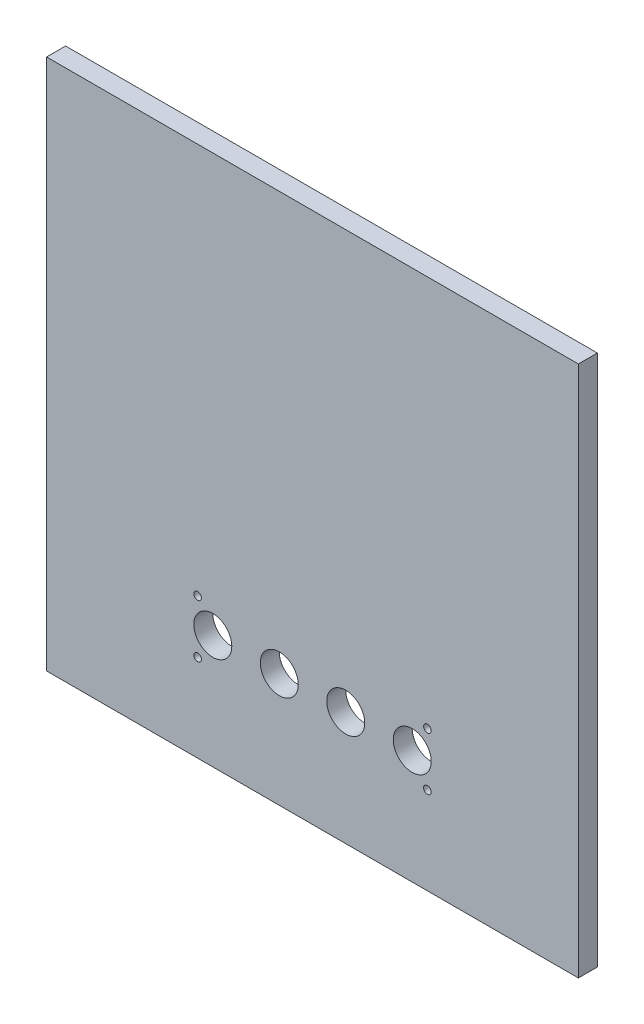
SolidWorks part; units mm, degrees
ref_plane "Front Plane" through (0, 0, 0) normal (0, 0, 1) x (1, 0, 0)
ref_plane "Top Plane" through (0, 0, 0) normal (0, 1, 0) x (1, 0, 0)
ref_plane "Right Plane" through (0, 0, 0) normal (1, 0, 0) x (0, 0, -1)
sketch "Sketch1" plane through (0, 0, 0) normal (0, 0, 1) x (1, 0, 0)
  line L1 (-109.0655, 43.855) -> (30.9345, 43.855)
  line L2 (-109.0655, 43.855) -> (-109.0655, -96.145)
  line L3 (-109.0655, -96.145) -> (30.9345, -96.145)
  line L4 (30.9345, 43.855) -> (30.9345, -96.145)
  line L5 (-73.3155, -55.145) -> (-4.8155, -55.145)
  line L6 (-73.3155, -55.145) -> (-73.3155, -77.145)
  line L7 (-73.3155, -77.145) -> (-4.8155, -77.145)
  line L8 (-4.8155, -55.145) -> (-4.8155, -77.145)
  circle A0 centre (-65.3155, -66.145) radius 5
  circle A1 centre (-47.8155, -66.145) radius 5
  circle A2 centre (-30.3155, -66.145) radius 5
  circle A3 centre (-12.8155, -66.145) radius 5
  circle A4 centre (-8.8155, -73.145) radius 1
  circle A5 centre (-69.3155, -73.145) radius 1
  circle A6 centre (-69.3155, -59.145) radius 1
  circle A7 centre (-8.8155, -59.145) radius 1
  dimension "D3" = 4
  dimension "D11" = 4
  dimension "D1" = 140
  dimension "D2" = 140
  dimension "D4" = 43.75
  dimension "D5" = 52.5
  dimension "D6" = 30
  dimension "D7" = 8
  dimension "D8" = 8
  dimension "D9" = 11
  dimension "D10" = 11
  dimension "D12" = 4
  dimension "D14" = 4
  dimension "D16" = 4
  dimension "D13" = 2
  dimension "D15" = 2
extrude "Boss-Extrude1" add sketch "Sketch1" along normal blind 5 contours L4 L1 L2 L3 L5 L8 L7 L6 region at (-39.0655, -22.8133, 0)
extrude "Boss-Extrude3" add sketch "Sketch1<4>" along normal blind 5 contours L8 L5 L6 L7 A7 A6 A5 A4 A3 A2 A1 A0 | L4 L1 L2 L3 L5 L8 L7 L6 region at (-39.0655, -22.8133, 0) region at (-39.0655, -66.145, 0)
sketch "Sketch1<4>" plane through (0, 0, 0) normal (0, 0, 1) x (1, 0, 0) same geometry as "Sketch1"
